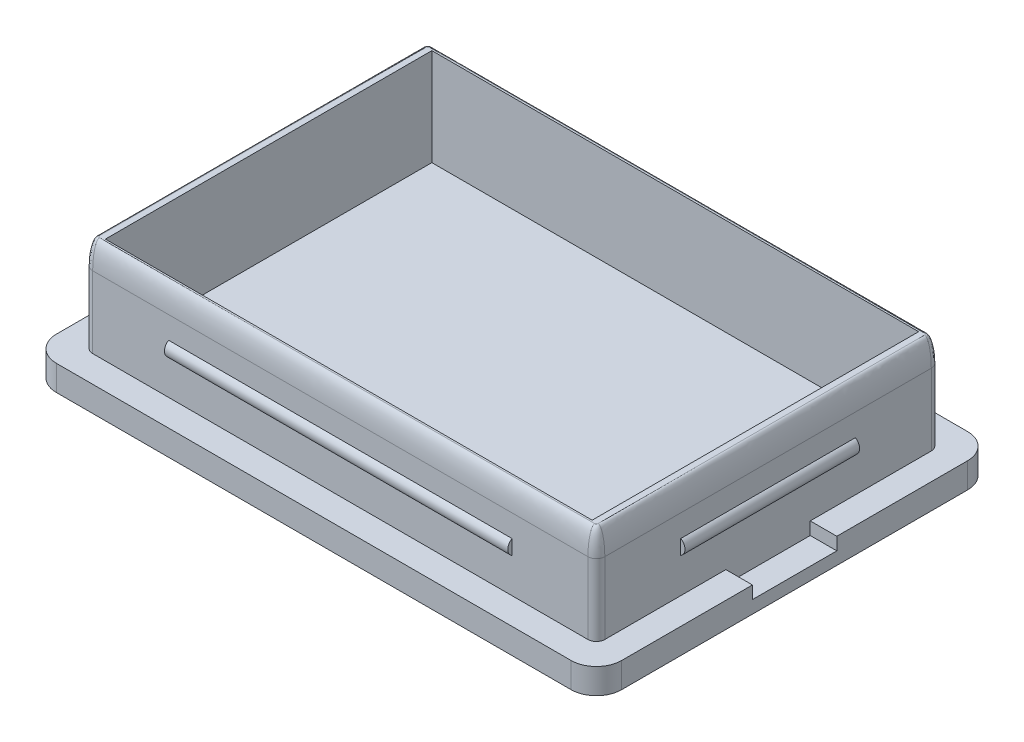
SolidWorks part; units mm, degrees
ref_plane "Front Plane" through (0, 0, 0) normal (0, 0, 1) x (1, 0, 0)
ref_plane "Top Plane" through (0, 0, 0) normal (0, 1, 0) x (1, 0, 0)
ref_plane "Right Plane" through (0, 0, 0) normal (1, 0, 0) x (0, 0, -1)
sketch "Sketch1" plane through (0, 0, 0) normal (0, 1, 0) x (1, 0, 0)
  line L1 (-30.5, 20.5) -> (30.5, 20.5)
  line L2 (-30.5, 20.5) -> (-30.5, -20.5)
  line L3 (-30.5, -20.5) -> (30.5, -20.5)
  line L4 (30.5, 20.5) -> (30.5, -20.5)
  line L5 (-30.5, 20.5) -> (30.5, -20.5) construction
  line L6 (-30.5, -20.5) -> (30.5, 20.5) construction
  point P0 (0, 0)
  dimension "D1" = 61
  dimension "D2" = 41
extrude "Boss-Extrude1" add sketch "Sketch1" along normal blind 23
shell "Shell1" thickness 3 removed face at (0, 23, 0) outward yes
sketch "Sketch2" plane through (0, 23, 0) normal (0, 1, 0) x (1, 0, 0)
  line L1 (-33.5, 23.5) -> (33.5, 23.5)
  line L2 (-33.5, 23.5) -> (-33.5, -23.5)
  line L3 (-33.5, -23.5) -> (33.5, -23.5)
  line L4 (33.5, 23.5) -> (33.5, -23.5)
extrude "Cut-Extrude1" cut sketch "Sketch2" against normal up to surface (23 mm away) up to face at (0, 0, 0)
sketch "Sketch3" plane through (0, 0, 0) normal (0, 1, 0) x (1, 0, 0)
  line L1 (-30.35, 20.35) -> (30.35, 20.35)
  line L2 (-30.35, 20.35) -> (-30.35, -20.35)
  line L3 (-30.35, -20.35) -> (30.35, -20.35)
  line L4 (30.5, 20.5) -> (-30.5, 20.5)
  line L5 (30.5, -20.5) -> (30.5, 20.5)
  line L6 (-30.5, -20.5) -> (30.5, -20.5)
  line L7 (-30.5, 20.5) -> (-30.5, -20.5)
  line L8 (30.5, 20.5) -> (-30.5, 20.5) construction
  line L9 (30.5, -20.5) -> (30.5, 20.5) construction
  line L10 (-30.5, -20.5) -> (30.5, -20.5) construction
  line L11 (-30.5, 20.5) -> (-30.5, -20.5) construction
  line L12 (30.35, 20.35) -> (30.35, -20.35)
  line L13 (-30.35, 20.35) -> (30.35, -20.35) construction
  line L14 (-30.35, -20.35) -> (30.35, 20.35) construction
  line L15 (-28.85, 19.35) -> (28.85, 19.35)
  line L16 (-28.85, 19.35) -> (-28.85, -19.35)
  line L17 (-28.85, -19.35) -> (28.85, -19.35)
  line L18 (28.85, 19.35) -> (28.85, -19.35)
  line L19 (-28.85, 19.35) -> (28.85, -19.35) construction
  line L20 (-28.85, -19.35) -> (28.85, 19.35) construction
  point P0 (0, 0)
  point P10 (0, 0)
  dimension "D2" = 0.15
  dimension "D3" = 0.15
  dimension "D4" = 1
  dimension "D5" = 1.5
  dimension "D1" = 0
extrude "Boss-Extrude2" add sketch "Sketch3" along normal blind 11.5
sketch "Sketch4" plane through (0, 0, 20.35) normal (0, 0, 1) x (1, 0, 0)
  line L1 (-30.35, 11.5) -> (-30.35, 0) construction
  line L2 (0, 0) -> (0, 16.7449) construction
  line L3 (25.85, 0) -> (-25.85, 0) construction
  circle A0 centre (-29.85, 5) radius 1
  circle A1 centre (29.85, 5) radius 1
  dimension "D2" = 2
  dimension "D3" = 0.5
  dimension "D1" = 5
extrude "Boss-Extrude3" add sketch "Sketch4" against normal offset from surface (20.7 mm away) 10 from offset 10 up to face at (0, 5.75, -20.35) offset against normal yes
sketch "Sketch5" plane through (30.35, 0, 0) normal (1, 0, 0) x (0, 0, -1)
  line L1 (-20.35, 11.5) -> (-20.35, 0) construction
  line L2 (0, 0) -> (0, 14.2856) construction
  line L3 (25.85, 0) -> (-25.85, 0) construction
  circle A0 centre (-19.85, 5) radius 1
  circle A1 centre (19.85, 5) radius 1
  line M4 (20.35, 0) -> (20.35, 11.5)
  line M6 (-20.35, 11.5) -> (-20.35, 0)
  dimension "D1" = 2
  dimension "D2" = 5
  dimension "D3" = 0.5
extrude "Boss-Extrude4" add sketch "Sketch5" against normal offset from surface (40.7 mm away) 10 from offset 10 contours A0 M6 | A1 M4 region at (30.35, 5, 20.555) region at (30.35, 5, -20.555) up to face at (-30.35, 5, 0) offset against normal yes
fillet "Fillet1" radius 3 4 edges at (33.5, -1.5, 23.5) (33.5, -1.5, -23.5) (-33.5, -1.5, -23.5) (-33.5, -1.5, 23.5)
fillet "Fillet2" radius 1 4 edges at (-30.35, 5.75, -20.35) (-30.35, 5.75, 20.35) (30.35, 5.75, 20.35) (30.35, 5.75, -20.35)
fillet "Fillet3" radius 3 8 edges at (30.35, 11.5, 0) (30.0571, 11.5, -20.0571) (30.0571, 11.5, 20.0571) (0, 11.5, -20.35) (0, 11.5, 20.35) (-30.0571, 11.5, -20.0571) (-30.0571, 11.5, 20.0571) (-30.35, 11.5, 0) second distance 0.8 first distance on face at (30.35, 5.75, 0) first distance on face at (29.9536, 5.75, -19.9536) first distance on face at (29.9536, 5.75, 19.9536) first distance on face at (0, 5, -20.35) first distance on face at (0, 5, 20.35) first distance on face at (-29.9536, 5.75, -19.9536) first distance on face at (-29.9536, 5.75, 19.9536) first distance on face at (-30.35, 5, 0)
sketch "Sketch6" plane through (33.5, 0, 0) normal (1, 0, 0) x (0, 0, -1)
  line L0 (25.85, 0) -> (-25.85, 0) construction
  line L1 (-5, -1.5) -> (5, -1.5)
  line L2 (-5, -1.5) -> (-5, 0)
  line L3 (-5, 0) -> (5, 0)
  line L4 (5, -1.5) -> (5, 0)
  line L5 (-5, -1.5) -> (5, 0) construction
  line L6 (-5, 0) -> (5, -1.5) construction
  point P0 (0, -0.75)
  dimension "D1" = 1.5
  dimension "D2" = 10
  dimension "D3" = 0
extrude "Cut-Extrude2" cut sketch "Sketch6" against normal up to surface (3.15 mm away) up to face at (30.35, 4.25, -4.8375)
sketch "Sketch7" plane through (-33.5, 0, 0) normal (-1, 0, 0) x (0, 0, 1)
  line L4 (-5, -1.5) -> (5, -1.5)
  line L5 (-5, 0) -> (-5, -1.5)
  line L6 (5, 0) -> (-5, 0)
  line L7 (5, -1.5) -> (5, 0)
  line L8 (-5, -1.5) -> (5, -1.5)
  line L9 (-5, 0) -> (-5, -1.5)
  line L10 (5, 0) -> (-5, 0)
  line L11 (5, -1.5) -> (5, 0)
  dimension "D1" = 0
extrude "Cut-Extrude3" cut sketch "Sketch7" against normal up to surface (3.15 mm away) up to face at (-30.35, 5, 0)
